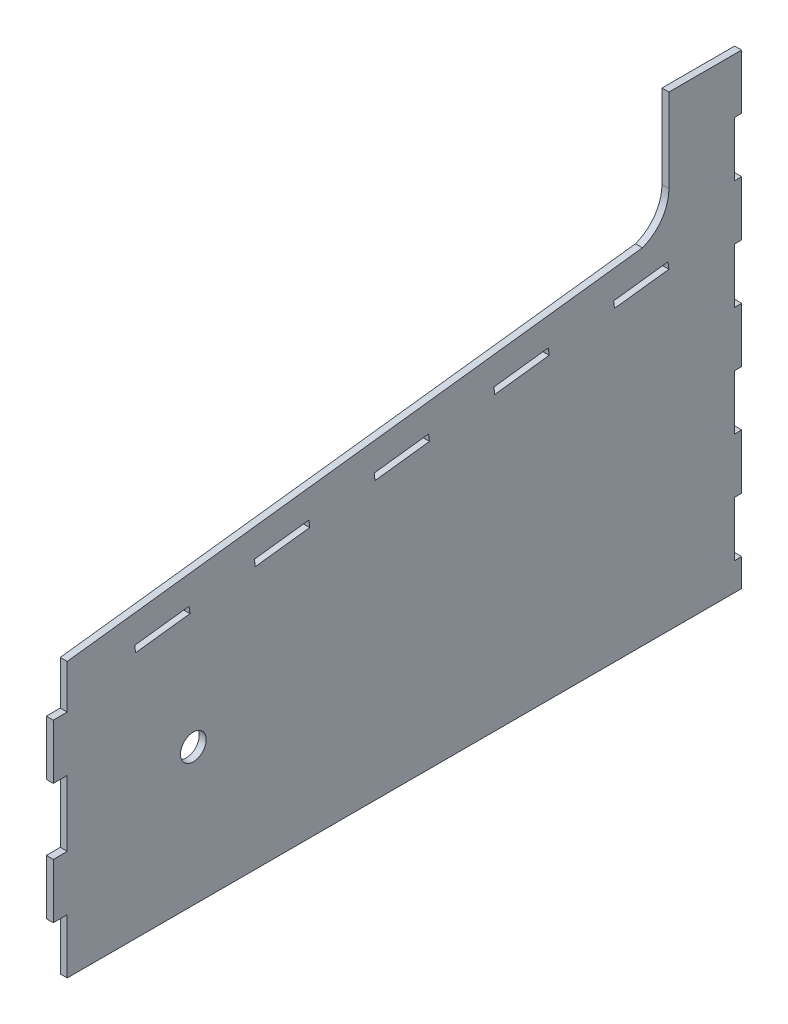
SolidWorks part; units mm, degrees
material "Beech"
ref_plane "Front Plane" through (0, 0, 0) normal (0, 0, 1) x (1, 0, 0)
ref_plane "Top Plane" through (0, 0, 0) normal (0, 1, 0) x (1, 0, 0)
ref_plane "Right Plane" through (0, 0, 0) normal (1, 0, 0) x (0, 0, -1)
sketch "Sketch1" plane through (0, 0, 0) normal (1, 0, 0) x (0, 0, -1)
  line L0 (0, 250) -> (524.53, 314.4042)
  line L1 (0, 0) -> (615, 0)
  line L2 (0, 0) -> (0, 50)
  line L7 (615, 425.32) -> (548.65, 425.32)
  line L8 (548.65, 349.09) -> (548.65, 425.32)
  line L9 (0, 250) -> (615, 250) construction
  line L10 (524.53, 314.4042) -> (615, 325.5125) construction
  line L11 (-12.7, 160) -> (-12.7, 210)
  line L12 (0, 50) -> (-12.7, 50)
  line L14 (0, 100) -> (-12.7, 100)
  line L15 (-12.7, 50) -> (-12.7, 100)
  line L16 (0, 160) -> (-12.7, 160)
  line L18 (0, 210) -> (-12.7, 210)
  line L19 (0, 210) -> (0, 250)
  line L21 (0, 100) -> (0, 160)
  line L40 (615, 425.32) -> (615, 0)
  arc A0 (524.53, 314.4042) -> (548.65, 349.09) centre (511.65, 349.09) ccw
  point P15 (615, 250)
  dimension "D4" = 37
  dimension "D1" = 615
  dimension "D2" = 250
  dimension "D3" = 66.35
  dimension "D5" = 7
  dimension "D6" = 175.32
  dimension "D7" = 76.23
  dimension "D8" = 12.7
  dimension "D9" = 50
  dimension "D10" = 50
  dimension "D11" = 2
  dimension "D12" = 40
extrude "Boss-Extrude1" add sketch "Sketch1" along normal blind 6.35
sketch "Sketch2" plane through (6.35, 0, 0) normal (1, 0, 0) x (0, 0, -1)
  line L0 (524.53, 314.4042) -> (615, 325.5125) construction
  line L2 (524.53, 314.4042) -> (0, 250) construction
  line L3 (0, 224.4093) -> (615, 299.9218) construction
  line L4 (0, 50) -> (0, 0) construction
  line L5 (61.5379, 231.9651) -> (62.3117, 225.6625)
  line L6 (62.3117, 225.6625) -> (111.939, 231.7559)
  line L7 (111.939, 231.7559) -> (111.1652, 238.0586)
  line L8 (111.1652, 238.0586) -> (61.5379, 231.9651)
  line L9 (220.3452, 251.4642) -> (170.7179, 245.3708)
  line L10 (170.7179, 245.3708) -> (171.4918, 239.0681)
  line L11 (171.4918, 239.0681) -> (221.1191, 245.1616)
  line L12 (221.1191, 245.1616) -> (220.3452, 251.4642)
  line L13 (329.5253, 264.8699) -> (279.898, 258.7764)
  line L14 (279.898, 258.7764) -> (280.6719, 252.4737)
  line L15 (280.6719, 252.4737) -> (330.2992, 258.5672)
  line L16 (330.2992, 258.5672) -> (329.5253, 264.8699)
  line L17 (438.7054, 278.2755) -> (389.0781, 272.182)
  line L18 (389.0781, 272.182) -> (389.852, 265.8794)
  line L19 (389.852, 265.8794) -> (439.4793, 271.9728)
  line L20 (439.4793, 271.9728) -> (438.7054, 278.2755)
  line L21 (547.8855, 291.6811) -> (498.2582, 285.5877)
  line L22 (498.2582, 285.5877) -> (499.032, 279.285)
  line L23 (499.032, 279.285) -> (548.6593, 285.3785)
  line L24 (548.6593, 285.3785) -> (547.8855, 291.6811)
  line L25 (0, 160) -> (0, 100) construction
  line L26 (0, 0) -> (615, 0) construction
  line L27 (615, 0) -> (615, 425.32) construction
  line L28 (615, 375.32) -> (608.65, 375.32)
  line L29 (615, 375.32) -> (615, 325.32)
  line L30 (615, 325.32) -> (608.65, 325.32)
  line L31 (608.65, 375.32) -> (608.65, 325.32)
  line L32 (615, 425.32) -> (548.65, 425.32) construction
  line L45 (615, 275.32) -> (615, 225.32)
  line L46 (615, 275.32) -> (608.65, 275.32)
  line L47 (608.65, 275.32) -> (608.65, 225.32)
  line L48 (615, 225.32) -> (608.65, 225.32)
  line L49 (615, 175.32) -> (615, 125.32)
  line L50 (615, 175.32) -> (608.65, 175.32)
  line L51 (608.65, 175.32) -> (608.65, 125.32)
  line L52 (615, 125.32) -> (608.65, 125.32)
  line L53 (615, 75.32) -> (615, 25.32)
  line L54 (615, 75.32) -> (608.65, 75.32)
  line L55 (608.65, 75.32) -> (608.65, 25.32)
  line L56 (615, 25.32) -> (608.65, 25.32)
  circle A0 centre (115, 125) radius 11.735
  dimension "D5" = 23.47
  dimension "D1" = 25.4
  dimension "D2" = 50
  dimension "D3" = 6.35
  dimension "D4" = 62
  dimension "D6" = 115
  dimension "D7" = 125
  dimension "D8" = 6.35
  dimension "D9" = 50
  dimension "D10" = 50
extrude "Cut-Extrude1" cut sketch "Sketch2" against normal blind 6.35
